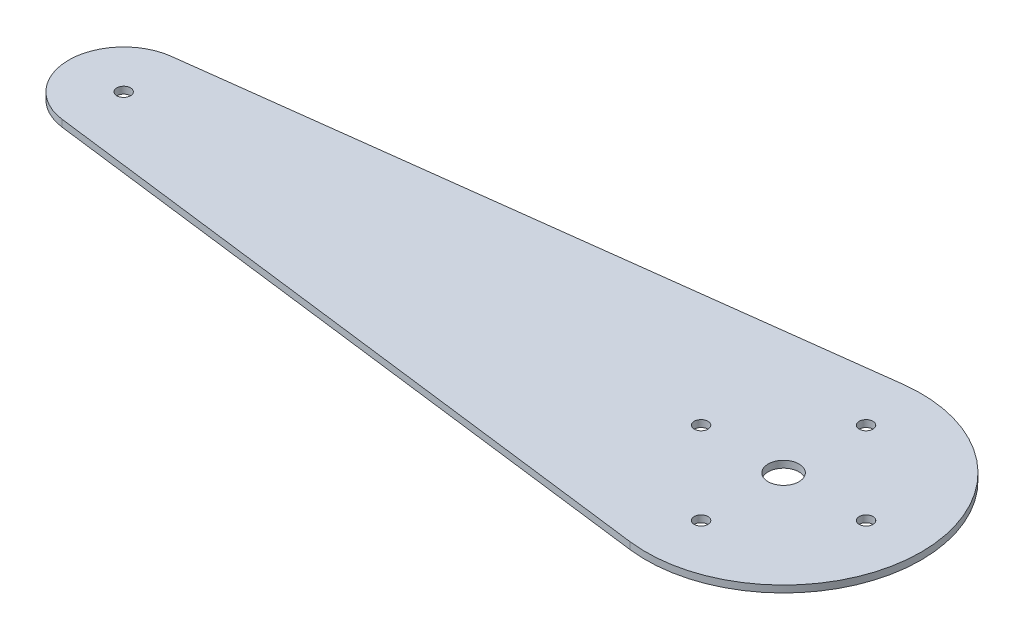
SolidWorks part; units mm, degrees
ref_plane "Front Plane" through (0, 0, 0) normal (0, 0, 1) x (1, 0, 0)
ref_plane "Top Plane" through (0, 0, 0) normal (0, 1, 0) x (1, 0, 0)
ref_plane "Right Plane" through (0, 0, 0) normal (1, 0, 0) x (0, 0, -1)
sketch "Sketch1" plane through (0, 0, 0) normal (0, 1, 0) x (1, 0, 0)
  line L0 (-153.9875, 12.6004) -> (-3.9688, 31.501)
  line L1 (-153.9875, -12.6004) -> (-3.9687, -31.501)
  line L2 (-111.3601, 0) -> (-50111.3601, 0) construction
  line L3 (0, -984.3615) -> (0, 49015.6385) construction
  line L4 (0, 0) -> (0, 19.05) construction
  line L5 (0, 0) -> (19.05, 0) construction
  arc A0 (-3.9687, -31.501) -> (-3.9688, 31.501) centre (0, 0) ccw
  arc A1 (-153.9875, 12.6004) -> (-153.9875, -12.6004) centre (-152.4, 0) ccw
  circle A2 centre (-152.4, 0) radius 1.5875
  circle A3 centre (0, 0) radius 3.556
  circle A4 centre (0, 19.05) radius 1.5875
  circle A5 centre (19.05, 0) radius 1.5875
  circle A6 centre (0, -19.05) radius 1.5875
  circle A7 centre (-19.05, 0) radius 1.5875
  dimension "D1" = 12.7
  dimension "D2" = 31.75
  dimension "D4" = 3.175
  dimension "D5" = 7.112
  dimension "D6" = 3.175
  dimension "D3" = 152.4
  dimension "D7" = 19.05
  dimension "D9" = 90
  dimension "D10" = 19.05
  dimension "D8" = 4
extrude "Boss-Extrude1" add sketch "Sketch1" along normal blind 1.5875
